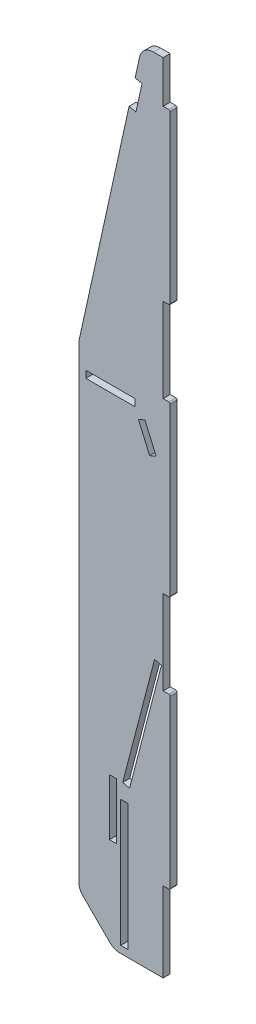
SolidWorks part; units mm, degrees
ref_plane "Front" through (0, 0, 0) normal (0, 0, 1) x (1, 0, 0)
ref_plane "Top" through (0, 0, 0) normal (0, 1, 0) x (1, 0, 0)
ref_plane "Right" through (0, 0, 0) normal (1, 0, 0) x (0, 0, -1)
sketch "Sketch1" plane through (0, 0, 0) normal (0, 0, 1) x (1, 0, 0)
  line L0 (80, 33.22) -> (20, 33.22)
  line L3 (20, 600) -> (80, 600)
  line L4 (80, 33.22) -> (80, 89.95)
  line L5 (20, 600) -> (20, 33.22)
  line L6 (80, 570.05) -> (80, 600)
  line L7 (80, 89.95) -> (85, 89.95)
  line L9 (80, 210.05) -> (85, 210.05)
  line L10 (85, 89.95) -> (85, 210.05)
  line L11 (80, 269.95) -> (85, 269.95)
  line L13 (80, 390.05) -> (85, 390.05)
  line L14 (85, 269.95) -> (85, 390.05)
  line L15 (80, 570.05) -> (85, 570.05)
  line L17 (80, 449.95) -> (85, 449.95)
  line L18 (85, 570.05) -> (85, 449.95)
  line L19 (80, 390.05) -> (80, 449.95)
  line L20 (80, 210.05) -> (80, 269.95)
  dimension "D1" = 600
  dimension "D2" = 120.1
  dimension "D3" = 33.22
  dimension "D4" = 20
  dimension "D5" = 60
  dimension "D6" = 120.1
  dimension "D7" = 120.1
  dimension "D8" = 5
  dimension "D9" = 5
  dimension "D10" = 5
  dimension "D11" = 29.95
  dimension "D12" = 59.9
  dimension "D13" = 59.9
extrude "Boss-Extrude1" add sketch "Sketch1" along normal blind 5
sketch "Sketch2" plane through (0, 0, 5) normal (0, 0, 1) x (1, 0, 0)
  line L0 (80, 600) -> (20, 600) construction
  line L1 (25, 380) -> (65, 380) construction
  line L2 (25, 380) -> (25, 375) construction
  line L3 (25, 375) -> (65, 375) construction
  line L4 (65, 380) -> (65, 375) construction
  line L5 (80, 33.22) -> (80, 89.95) construction
  line L6 (65, 375) -> (77, 347.5045) construction
  line L7 (77, 347.5045) -> (72.4174, 345.5045) construction
  line L8 (72.4174, 345.5045) -> (60.4174, 373) construction
  line L9 (60.4174, 373) -> (65, 375) construction
  line L10 (67, 370.4174) -> (62.4174, 368.4174)
  line L11 (62.4174, 368.4174) -> (70.4174, 350.0871)
  line L12 (70.4174, 350.0871) -> (75, 352.0871)
  line L13 (75, 352.0871) -> (67, 370.4174)
  line L14 (80, 230) -> (75.1609, 231.258) construction
  line L15 (75.1609, 231.258) -> (50, 134.4751) construction
  line L16 (50, 134.4751) -> (54.8391, 133.2171) construction
  line L17 (54.8391, 133.2171) -> (80, 230) construction
  line L18 (73.9028, 226.4189) -> (51.258, 139.3143)
  line L19 (73.9028, 226.4189) -> (78.742, 225.1609)
  line L20 (51.258, 139.3143) -> (56.0972, 138.0562)
  line L21 (78.742, 225.1609) -> (56.0972, 138.0562)
  line L23 (54.8391, 133.2171) -> (49.8391, 133.2171) construction
  line L24 (54.8391, 133.2171) -> (54.8391, 33.2171) construction
  line L25 (54.8391, 33.2171) -> (49.8391, 33.2171) construction
  line L26 (49.8391, 133.2171) -> (49.8391, 33.2171) construction
  line L27 (49.8391, 128.2171) -> (54.8391, 128.2171)
  line L28 (49.8391, 128.2171) -> (49.8391, 38.2171)
  line L29 (49.8391, 38.2171) -> (54.8391, 38.2171)
  line L30 (54.8391, 128.2171) -> (54.8391, 38.2171)
  line L31 (41.8391, 139.3143) -> (46.8391, 139.3143)
  line L32 (41.8391, 139.3143) -> (41.8391, 99.3143)
  line L33 (41.8391, 99.3143) -> (46.8391, 99.3143)
  line L34 (46.8391, 139.3143) -> (46.8391, 99.3143)
  line L35 (60, 380) -> (25, 380)
  line L36 (60, 380) -> (60, 375)
  line L37 (60, 375) -> (25, 375)
  line L38 (25, 380) -> (25, 375)
  point P30 (52.3391, 33.2171)
  dimension "D1" = 220
  dimension "D2" = 5
  dimension "D3" = 5
  dimension "D4" = 15
  dimension "D5" = 5
  dimension "D6" = 20
  dimension "D7" = 3
  dimension "D8" = 30
  dimension "D9" = 5
  dimension "D10" = 5
  dimension "D11" = 370
  dimension "D12" = 30
  dimension "D13" = 100
  dimension "D14" = 5
  dimension "D15" = 5
  dimension "D16" = 5
  dimension "D17" = 100
  dimension "D18" = 5
  dimension "D19" = 5
  dimension "D20" = 5
  dimension "D21" = 3
  dimension "D22" = 40
  dimension "D23" = 35
extrude "Cut-Extrude1" cut sketch "Sketch2" against normal blind 10
sketch "Sketch3" plane through (0, 0, 5) normal (0, 0, 1) x (1, 0, 0)
  line L0 (20, 395) -> (65, 600)
  line L1 (20, 600) -> (20, 33.22) construction
  line L2 (80, 600) -> (20, 600) construction
  line L4 (20, 395) -> (1.5136, 616.0876)
  line L5 (1.5136, 616.0876) -> (65, 600)
  line L6 (45, 33.22) -> (20, 58.22)
  line L7 (20, 33.22) -> (80, 33.22) construction
  line L8 (20, 58.22) -> (13.4525, 20.5561)
  line L9 (13.4525, 20.5561) -> (45, 33.22)
  line L10 (60, 380) -> (25, 380) construction
  dimension "D1" = 15
  dimension "D2" = 15
  dimension "D3" = 25
  dimension "D4" = 25
extrude "Cut-Extrude2" cut sketch "Sketch3" against normal blind 10
fillet "Fillet1" radius 1 6 edges at (85, 570.05, 2.5) (85, 449.95, 2.5) (85, 390.05, 2.5) (85, 269.95, 2.5) (85, 210.05, 2.5) (85, 89.95, 2.5)
fillet "Fillet2" radius 10 4 edges at (65, 600, 2.5) (20, 395, 2.5) (20, 58.22, 2.5) (45, 33.22, 2.5)
sketch "Sketch4" plane through (0, 0, 5) normal (0, 0, 1) x (1, 0, 0)
  line L0 (61.1315, 582.3766) -> (66.0152, 581.3046) construction
  line L1 (61.1315, 582.3766) -> (54.6992, 553.0743) construction
  line L2 (66.0152, 581.3046) -> (59.583, 552.0023) construction
  line L3 (54.6992, 553.0743) -> (59.583, 552.0023) construction
  line L4 (60.0594, 577.4929) -> (64.9431, 576.4209)
  line L5 (60.0594, 577.4929) -> (55.7713, 557.958)
  line L6 (64.9431, 576.4209) -> (60.655, 556.886)
  line L7 (55.7713, 557.958) -> (60.655, 556.886)
  dimension "D1" = 30
  dimension "D2" = 5
  dimension "D3" = 20
  dimension "D4" = 5
  dimension "D5" = 10
extrude "Cut-Extrude3" cut sketch "Sketch4" against normal blind 10
